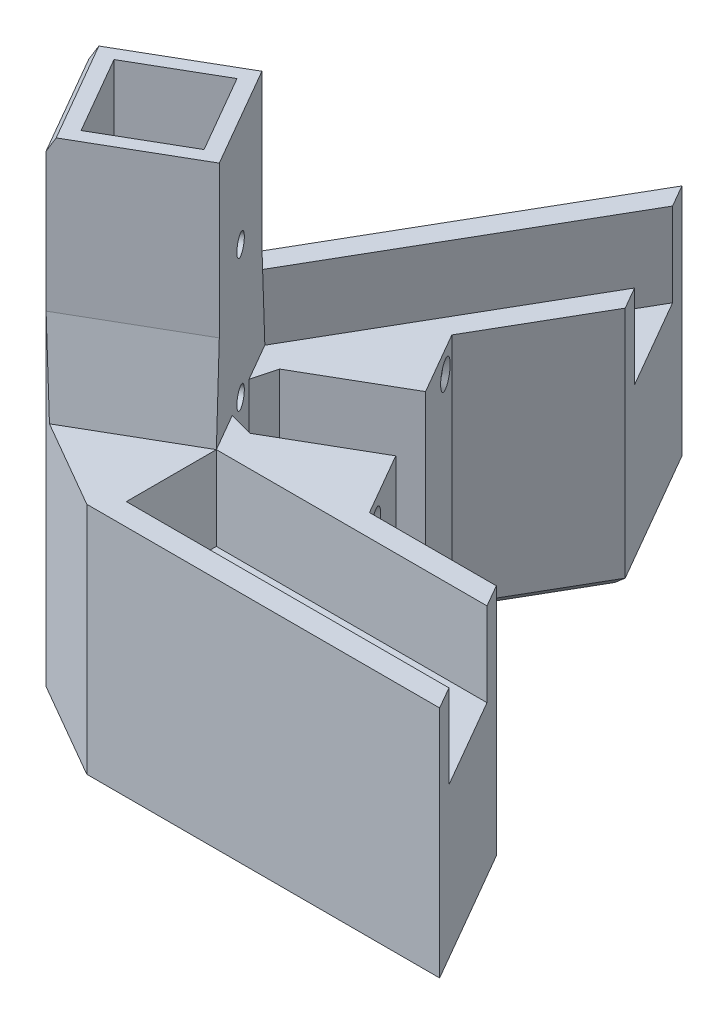
SolidWorks part; units mm, degrees
other "Markup1"
sketch "Sketch26" plane through (25.6218, 0, -129.9038) normal (-0.1134, -0.9932, -0.0259) x (0.9576, -0.1162, 0.2636)
ref_plane "Front Plane" through (0, 0, 0) normal (0, 0, 1) x (1, 0, 0)
ref_plane "Top Plane" through (0, 0, 0) normal (0, 1, 0) x (1, 0, 0)
ref_plane "Right Plane" through (0, 0, 0) normal (1, 0, 0) x (0, 0, -1)
sketch "Sketch1" plane through (0, 0, 0) normal (0, 1, 0) x (1, 0, 0)
  line L0 (0, 0) -> (150, 0)
  line L1 (0, 0) -> (75, 129.9038)
  line L2 (75, 129.9038) -> (150, 0)
  dimension "D1" = 60
  dimension "D2" = 150
  dimension "D3" = 60
sketch "Sketch2" plane through (0, 0, 0) normal (0, 1, 0) x (1, 0, 0)
  line L1 (74.2, 5.2) -> (174.2, 5.2) construction
  line L2 (74.2, 5.2) -> (74.2, 25.2) construction
  line L3 (74.2, 25.2) -> (174.2, 25.2) construction
  line L4 (174.2, 5.2) -> (174.2, 25.2) construction
  line L5 (41.6033, 61.6591) -> (91.6033, 148.2616) construction
  line L6 (91.6033, 148.2616) -> (108.9238, 138.2616) construction
  line L7 (108.9238, 138.2616) -> (58.9238, 51.6591) construction
  line L8 (58.9238, 51.6591) -> (41.6033, 61.6591) construction
  line L9 (0, 0) -> (150, 0) construction
  line L10 (109.197, 138.3348) -> (58.997, 51.3859)
  line L11 (58.997, 51.3859) -> (41.3301, 61.5859)
  line L12 (41.3301, 61.5859) -> (91.5301, 148.5348)
  line L13 (91.5301, 148.5348) -> (109.197, 138.3348)
  line L14 (74, 25.4) -> (174.4, 25.4)
  line L15 (174.4, 5) -> (174.4, 25.4)
  line L16 (74, 5) -> (174.4, 5)
  line L17 (74, 5) -> (74, 25.4)
  line L18 (0, 0) -> (75, 129.9038) construction
  dimension "D1" = 20
  dimension "D2" = 5
  dimension "D3" = 74
  dimension "D4" = 20
  dimension "D5" = 74
  dimension "D6" = 5
  dimension "D7" = 100
  dimension "D8" = 100
  dimension "D9" = 0.2
  dimension "D10" = 0.2
sketch "Sketch4" plane through (0, 0, 0) normal (0, 1, 0) x (1, 0, 0)
  line L4 (0, 0) -> (54.7796, 31.6328) construction
  line L6 (0, 0) -> (53.0061, 91.8093) construction
  line L7 (68.4402, 27.9736) -> (51.1204, 17.9723) construction
  line L8 (68.4402, 27.9736) -> (58.4388, 45.2934) construction
  line L9 (58.4388, 45.2934) -> (41.1191, 35.292) construction
  line L10 (51.1204, 17.9723) -> (41.1191, 35.292) construction
  line L11 (68.4402, 27.9736) -> (41.1191, 35.292) construction
  line L12 (58.4388, 45.2934) -> (51.1204, 17.9723) construction
  line L13 (58.512, 45.5666) -> (40.8459, 35.3652)
  line L15 (0, 0) -> (131.24, 0) construction
  line L17 (51.0473, 17.6991) -> (40.8459, 35.3652)
  line L18 (68.7134, 27.9005) -> (51.0473, 17.6991)
  line L19 (68.7134, 27.9005) -> (58.512, 45.5666)
  point P0 (54.7796, 31.6328)
  dimension "D1" = 20
  dimension "D2" = 20
  dimension "D3" = 30.005
  dimension "D4" = 0.2
  dimension "D5" = 63.2569
  dimension "D6" = 60
ref_plane "Plane1" through (4.3301, 0, 2.5) normal (0.866, 0, 0.5) x (0.5, 0, -0.866)
ref_plane "Plane2" through (21.997, 0, 12.7) normal (-0.866, 0, -0.5) x (-0.5, 0, 0.866)
ref_plane "Plane3" through (0, 0, -25.4) normal (0, 0, 1) x (1, 0, 0)
ref_plane "Plane4" through (0, 0, -5) normal (0, 0, 1) x (1, 0, 0)
ref_plane "Plane6" through (-5.1007, 0, -8.8331) normal (-0.5001, 0, -0.866) x (-0.866, 0, 0.5001)
ref_plane "Plane7" through (5.1007, 0, 8.8331) normal (-0.5001, 0, -0.866) x (-0.866, 0, 0.5001)
extrude "Boss-Extrude1" add sketch "Sketch1" against normal blind 55
extrude "Cut-Extrude2" cut sketch "Sketch4" against normal through all and the other way through all
extrude "Cut-Extrude3" cut sketch "Sketch2" against normal blind 19
sketch "Sketch27" plane through (0, 0, 0) normal (0, 1, 0) x (1, 0, 0)
  line L0 (92.5514, 99.5038) -> (61.884, 46.3862)
  line L1 (135.3353, 25.4) -> (89.6647, 104.5038) construction
  line L2 (61.884, 46.3862) -> (71.1153, 30.4)
  line L3 (71.1153, 30.4) -> (132.4486, 30.4)
  line L4 (58.997, 51.3859) -> (89.6647, 104.5038) construction
  line L5 (135.3353, 25.4) -> (74, 25.4) construction
  line L6 (58.512, 45.5666) -> (68.7134, 27.9005) construction
  line L7 (58.997, 51.3859) -> (89.6647, 104.5038) construction
  line L8 (74, 25.4) -> (135.3353, 25.4) construction
  dimension "D1" = 5
  dimension "D2" = 5
  dimension "D3" = 3.33
extrude "Cut-Extrude4" cut sketch "Sketch27" against normal through all and the other way through all
sketch "Sketch28" plane through (0, 0, 0) normal (0, 1, 0) x (1, 0, 0)
  line L1 (92.5514, 99.5038) -> (61.884, 46.3862) construction
  line L2 (71.1153, 30.4) -> (132.4486, 30.4) construction
  line L3 (61.884, 46.3862) -> (71.1153, 30.4) construction
  line L5 (61.884, 46.3862) -> (78.1721, 74.598)
  line L6 (78.1721, 74.598) -> (86.3161, 60.4947)
  line L7 (103.6944, 30.4) -> (71.1153, 30.4)
  line L8 (86.3161, 60.4947) -> (61.884, 46.3862)
  line L9 (71.1153, 30.4) -> (95.5474, 44.5085)
  line L10 (95.5474, 44.5085) -> (103.6944, 30.4)
  dimension "D1" = 105
sketch "Sketch36" plane through (0, 0, 0) normal (0, 1, 0) x (1, 0, 0)
  line L0 (0, 0) -> (27.7444, 48.0548)
  line L1 (75, 129.9038) -> (0, 0) construction
  line L2 (27.7444, 48.0548) -> (55.4939, 0)
  line L3 (0, 0) -> (150, 0) construction
  line L4 (55.4939, 0) -> (0, 0)
  line L5 (51.0473, 17.6991) -> (40.8459, 35.3652) construction
  dimension "D1" = 5
extrude "Cut-Extrude12" cut sketch "Sketch36" against normal through all
sketch "Sketch37" plane through (0, 0, 0) normal (0, 1, 0) x (1, 0, 0)
  line L0 (35.0157, 35.4628) -> (59.8955, 49.8298)
  line L1 (61.884, 46.3862) -> (71.1153, 30.4) construction
  line L3 (55.4939, 0) -> (27.7444, 48.0548) construction
  line L6 (40.8459, 35.3652) -> (58.512, 45.5666) construction
  line L7 (48.2175, 12.6008) -> (73.0973, 26.9677)
  line L9 (68.7134, 27.9005) -> (51.0473, 17.6991) construction
  line L10 (59.8955, 49.8298) -> (73.0973, 26.9677)
  line L14 (58.512, 45.5666) -> (68.7134, 27.9005) construction
  line L15 (35.0157, 35.4628) -> (48.2175, 12.6008)
  line L16 (58.512, 45.5666) -> (40.8459, 35.3652)
  line L17 (40.8459, 35.3652) -> (51.0473, 17.6991)
  line L18 (51.0473, 17.6991) -> (68.7134, 27.9005)
  line L19 (68.7134, 27.9005) -> (58.512, 45.5666)
  dimension "D1" = 3
  dimension "D2" = 3
extrude "Boss-Extrude2" add sketch "Sketch37" along normal blind 55
chamfer "Chamfer1" distance 14.54 angle 30 1 edges at (27.7444, -27.5, -48.0548) first distance on face at (41.6179, 0, -24.0296)
chamfer "Chamfer8" distance 14.54 angle 30 1 edges at (55.4939, -27.5, 0) first distance on face at (102.747, -27.5, 0)
chamfer "Chamfer7" distance 1.81 angle 85 2 edges at (60.6574, 0, -19.7842) (47.4556, 0, -42.6463) first distance on face at (93.053, 0, -15.7965) first distance on face at (60.2049, 0, -72.6886)
chamfer "Chamfer10" distance 2.9 angle 30 1 edges at (41.6166, 55, -24.0318) first distance on face at (41.6177, 10.3308, -24.03)
extrude "Boss-Extrude4" add sketch "Sketch28" against normal up to surface (55 mm away) up to face at (77.1284, -55, -44.5295)
sketch "Sketch39" plane through (90.9285, 0, -52.5072) normal (0.866, 0, -0.5001) x (-0.5001, 0, -0.866)
  line L0 (-25.5284, 0) -> (-9.2366, 0) construction
  line L1 (-21.5, -48) -> (21.5, -48) construction
  line L2 (-21.5, -48) -> (-21.5, -5) construction
  line L3 (-21.5, -5) -> (21.5, -5) construction
  line L4 (21.5, -48) -> (21.5, -5) construction
  line L5 (-21.5, -48) -> (21.5, -5) construction
  line L6 (-21.5, -5) -> (21.5, -48) construction
  circle A0 centre (-21.5, -5) radius 1.95
  circle A1 centre (21.5, -5) radius 1.95
  circle A2 centre (21.5, -48) radius 1.95
  circle A3 centre (-21.5, -48) radius 1.95
  point P0 (0, -26.5)
  dimension "D4" = 3.9
  dimension "D1" = 43
  dimension "D2" = 43
  dimension "D3" = 5
extrude "Cut-Extrude13" cut sketch "Sketch39" against normal blind 11
sketch "Sketch40" plane through (0, -19, 0) normal (0, 1, 0) x (1, 0, 0)
  line L0 (50.1636, 56.4859) -> (83.7757, 114.7038) construction
  line L1 (41.3301, 61.5859) -> (58.997, 51.3859) construction
  line L2 (89.6647, 104.5038) -> (77.8868, 124.9038) construction
  circle A0 centre (76.2757, 101.7134) radius 2.3
  circle A1 centre (57.6636, 69.4763) radius 2.3
  dimension "D1" = 4.6
  dimension "D2" = 15
  dimension "D3" = 15
extrude "Cut-Extrude14" cut sketch "Sketch40" against normal through all
sketch "Sketch41" plane through (0, -19, 0) normal (0, 1, 0) x (1, 0, 0)
  line L0 (74, 15.2) -> (141.2243, 15.2) construction
  line L1 (74, 25.4) -> (74, 5) construction
  line L2 (147.1132, 5) -> (135.3353, 25.4) construction
  circle A0 centre (89, 15.2) radius 2.3
  circle A1 centre (126.2243, 15.2) radius 2.3
  dimension "D1" = 4.6
  dimension "D2" = 15
  dimension "D3" = 15
extrude "Cut-Extrude15" cut sketch "Sketch41" against normal through all
ref_plane "Plane8" through (0, -24, 0) normal (0, 1, 0) x (1, 0, 0)
sketch "Sketch42" plane through (0, -24, 0) normal (0, 1, 0) x (1, 0, 0)
  circle A0 centre (76.2757, 101.7134) radius 5
  circle A1 centre (57.6636, 69.4763) radius 5
  circle A2 centre (89, 15.2) radius 5
  circle A3 centre (126.2243, 15.2) radius 5
  dimension "D1" = 10
extrude "Cut-Extrude16" cut sketch "Sketch42" against normal through all
chamfer "Chamfer6" distance 1 angle 45 4 edges at (49.6789, -55, -40.4659) (45.9466, -55, -26.5321) (59.8803, -55, -22.7998) (63.6127, -55, -36.7335)
chamfer "Chamfer13" distance 2 angle 45 4 edges at (126.2243, -55, -10.2) (89, -55, -10.2) (76.2757, -55, -96.7134) (57.6636, -55, -64.4763)
chamfer "Chamfer14" distance 4 angle 45 2 edges at (61.884, -27.5, -46.3862) (71.1153, -27.5, -30.4)
sketch "Sketch35" plane through (45.9466, 0, -26.5321) normal (0.866, 0, -0.5001) x (-0.5001, 0, -0.866)
  line L0 (0, 0) -> (0, -55) construction
  circle A0 centre (0, -30) radius 2.3
  circle A1 centre (0, 0) radius 2.3
  circle A2 centre (0, 30) radius 2.3
  point P2 (0, 0)
  dimension "D3" = 4.6
  dimension "D1" = 30
  dimension "D4" = 30
extrude "Cut-Extrude11" cut sketch "Sketch35" along normal through all
chamfer "Chamfer15" distance 1 angle 45 4 edges at (79.2019, -48, -72.8146) (100.7048, -48, -35.5772) (100.7048, -5, -35.5772) (79.2019, -5, -72.8146)
chamfer "Chamfer12" distance 2 angle 45 16 edges at (85.0634, -55, -38.4544) (99.6209, -55, -37.4542) (118.0715, -55, -30.4) (141.2243, -55, -15.2) (110.017, -55, 0) (59.1279, -55, -6.2966) (41.6187, -55, -24.0282) (35.0144, -55, -48.0542) (55.0067, -55, -95.2744) (83.7757, -55, -114.7038) (85.3618, -55, -87.0509) (82.2441, -55, -67.5463) (75.832, -55, -54.4406) (66.4997, -55, -38.3931) (64.6161, -55, -45.6544) (71.8472, -55, -33.1321)
